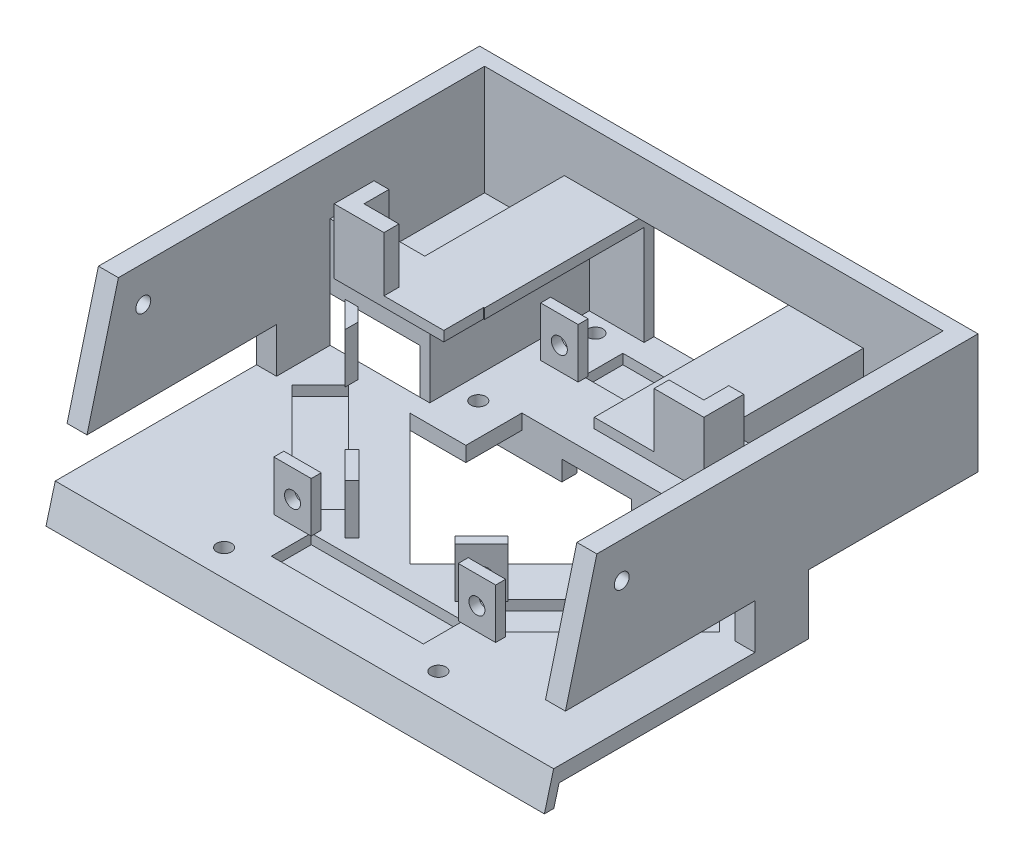
SolidWorks part; units mm, degrees
ref_plane "Plano frontal" through (0, 0, 0) normal (0, 0, 1) x (1, 0, 0)
ref_plane "Plano superior" through (0, 0, 0) normal (0, 1, 0) x (1, 0, 0)
ref_plane "Plano direito" through (0, 0, 0) normal (1, 0, 0) x (0, 0, -1)
sketch "Esboço1" plane through (0, 0, 0) normal (1, 0, 0) x (0, 0, -1)
  line L0 (0, 0) -> (52.75, 0)
  line L1 (0, 0) -> (17.0884, 63.7748)
  line L2 (52.75, 0) -> (52.75, 3)
  line L3 (52.75, 3) -> (3.9097, 3)
  line L4 (17.0884, 63.7748) -> (19.9862, 62.9984)
  line L5 (19.9862, 62.9984) -> (3.9097, 3)
  dimension "D1" = 75
  dimension "D2" = 52.75
  dimension "D3" = 3
  dimension "D4" = 3
extrude "Ressalto-extrusão1" add sketch "Esboço1" along normal blind 100
sketch "Esboço3" plane through (0, 3, 0) normal (0, 1, 0) x (1, 0, 0)
  line L0 (100, 52.75) -> (0, 52.75) construction
  line L1 (22, 52.75) -> (78, 52.75)
  line L2 (22, 52.75) -> (22, 86.75)
  line L3 (22, 86.75) -> (78, 86.75)
  line L4 (78, 52.75) -> (78, 86.75)
  dimension "D1" = 56
  dimension "D2" = 34
  dimension "D3" = 22
extrude "Ressalto-extrusão2" add sketch "Esboço3" against normal blind 3
sketch "Esboço5" plane through (100, 0, 0) normal (1, 0, 0) x (0, 0, -1)
  line L1 (0, 0) -> (52.75, 0) construction
  line L3 (3.9097, 3) -> (1.6041, 3)
  line L4 (1.6041, 3) -> (0.8002, 0)
  line L5 (0.8002, 0) -> (0, 0)
  line L6 (0, 0) -> (17.0884, 63.7748)
  line L7 (17.0884, 63.7748) -> (19.9862, 62.9984)
  line L8 (19.9862, 62.9984) -> (3.9097, 3)
extrude "Corte-extrusão1" cut sketch "Esboço5" against normal blind 100
sketch "Esboço6" plane through (100, 0, 0) normal (1, 0, 0) x (0, 0, -1)
  line L0 (1.649, -3.9196) -> (-0.25, -3.9196)
  line L1 (-0.25, -3.9196) -> (0.8002, 0)
  line L2 (0.8002, 0) -> (2.7002, 0)
  line L3 (0.8002, 0) -> (52.75, 0) construction
  line L4 (2.7002, 0) -> (1.649, -3.9196)
  dimension "D1" = 1.9
extrude "Ressalto-extrusão4" add sketch "Esboço6" against normal blind 100
sketch "Esboço13" plane through (0, 3, 0) normal (0, 1, 0) x (1, 0, 0)
  line L0 (35, 37.75) -> (50, 22.75)
  line L1 (35, 60.2384) -> (65, 60.2384)
  line L2 (35, 60.2384) -> (35, 48.9942)
  line L4 (65, 60.2384) -> (65, 48.9942)
  line L5 (65, 37.75) -> (50, 22.75)
  line L6 (35, 37.75) -> (23.7558, 48.9942)
  line L7 (23.7558, 48.9942) -> (35, 48.9942)
  line L8 (65, 37.75) -> (76.2442, 48.9942)
  line L9 (76.2442, 48.9942) -> (65, 48.9942)
extrude "Corte-extrusão3" cut sketch "Esboço13" against normal through all
sketch "Esboço14" plane through (78, 0, 0) normal (1, 0, 0) x (0, 0, -1)
  line L0 (52.75, 0) -> (86.75, 0) construction
  line L1 (60.2384, -4.9963) -> (63.2384, -4.9963)
  line L2 (60.2384, -4.9963) -> (60.2384, 0)
  line L3 (60.2384, 0) -> (63.2384, 0)
  line L5 (63.2384, 0) -> (65.5807, 0)
  line L6 (79.2384, -4.9963) -> (76.2384, -4.9963)
  line L7 (79.2384, -4.9963) -> (79.2384, 0.0037)
  line L8 (79.2384, 0.0037) -> (76.2384, 0.0037)
  line L10 (76.2384, 0.0037) -> (73.8962, 0)
  arc A1 (76.2384, -4.9963) -> (73.8962, 0) centre (69.7384, -4.9963) ccw
  arc A2 (65.5807, 0) -> (63.2384, -4.9963) centre (69.7384, -4.9963) ccw
  dimension "D1" = 3
  dimension "D2" = 5
extrude "Ressalto-extrusão7" add sketch "Esboço14" against normal blind 56
sketch "Esboço15" plane through (0, 3, 0) normal (0, 1, 0) x (1, 0, 0)
  line L0 (22, 60.2384) -> (28.5, 60.2384) construction
  line L1 (22, 60.2384) -> (35, 60.2384) construction
  line L2 (22, 79.2384) -> (28.5, 79.2384) construction
  line L4 (78, 79.2384) -> (22, 79.2384) construction
  line L6 (28.5, 79.2384) -> (28.5, 81.4934) construction
  line L7 (28.5, 60.2384) -> (28.5, 57.9834) construction
  line L8 (78, 79.2384) -> (71.5, 79.2384) construction
  line L9 (28.5, 81.4934) -> (71.5, 81.4934) construction
  line L10 (71.5, 81.4934) -> (71.5, 57.9834) construction
  circle A0 centre (28.5, 81.4934) radius 1.5
  circle A1 centre (28.5, 57.9834) radius 1.5
  circle A2 centre (71.5, 81.4934) radius 1.5
  circle A3 centre (71.5, 57.9834) radius 1.5
  dimension "D2" = 3
  dimension "D4" = 3
  dimension "D6" = 3
  dimension "D7" = 3
  dimension "D1" = 2.255
  dimension "D3" = 2.255
  dimension "D5" = 6.5
extrude "Corte-extrusão4" cut sketch "Esboço15" against normal through all
sketch "Esboço16" plane through (0, 3, 0) normal (0, 1, 0) x (1, 0, 0)
  line L0 (28.5, 57.9834) -> (28.5, 6.9834) construction
  line L1 (71.5, 57.9834) -> (71.5, 6.9834) construction
  circle A0 centre (28.5, 6.9834) radius 1.5
  circle A2 centre (71.5, 6.9834) radius 1.5
  dimension "D3" = 3
  dimension "D4" = 3
  dimension "D1" = 51
  dimension "D2" = 51
extrude "Corte-extrusão5" cut sketch "Esboço16" against normal through all
sketch "Esboço17" plane through (0, 3, 0) normal (0, 1, 0) x (1, 0, 0)
  line L3 (34.75, 10.2166) -> (65.25, 10.2166)
  line L4 (34.75, 10.2166) -> (34.75, 18.2166)
  line L5 (34.75, 18.2166) -> (65.25, 18.2166)
  line L6 (65.25, 10.2166) -> (65.25, 18.2166)
  dimension "D3" = 30.5
  dimension "D4" = 8
extrude "Corte-extrusão6" cut sketch "Esboço17" against normal blind 2
sketch "Esboço18" plane through (0, 3, 0) normal (0, 1, 0) x (1, 0, 0)
  line L0 (7.105, 41.9998) -> (7.4586, 42.3533)
  line L2 (7.105, 41.9998) -> (28.6718, 20.433)
  line L3 (28.6718, 20.433) -> (34.3286, 26.0899)
  line L8 (7.4586, 42.3533) -> (12.7619, 47.6566)
  line L10 (12.8706, 47.5479) -> (34.3286, 26.0899)
  line L11 (12.7619, 47.6566) -> (12.8706, 47.5479)
  line L13 (0, 41.9998) -> (18.4187, 41.9998) construction
  line L16 (0, 52.75) -> (0, 1.6041) construction
  line L17 (92.89, 41.9998) -> (87.2331, 47.6566)
  line L19 (87.2331, 47.6566) -> (65.6664, 26.0899)
  line L21 (65.6664, 26.0899) -> (71.3232, 20.433)
  line L22 (71.3232, 20.433) -> (92.89, 41.9998)
  dimension "D1" = 8
  dimension "D2" = 0.5
  dimension "D4" = 30.5
extrude "Corte-extrusão7" cut sketch "Esboço18" against normal blind 2
sketch "Esboço19" plane through (0, 3, 0) normal (0, 1, 0) x (1, 0, 0)
  line L6 (65.25, 72.75) -> (34.75, 72.75)
  line L7 (65.25, 72.75) -> (65.25, 80.75)
  line L8 (65.25, 80.75) -> (34.75, 80.75)
  line L9 (34.75, 72.75) -> (34.75, 80.75)
  dimension "D3" = 8
  dimension "D4" = 30.5
extrude "Corte-extrusão8" cut sketch "Esboço19" against normal blind 2
sketch "Esboço20" plane through (0, 0, -60.2384) normal (0, 0, 1) x (1, 0, 0)
  line L0 (22, -4.9963) -> (50, -4.9963) construction
  line L10 (50, -4.9963) -> (43, -4.9963)
  line L11 (43, -4.9963) -> (43, -0.9963)
  line L12 (43, -0.9963) -> (57, -0.9963)
  line L13 (57, -0.9963) -> (57, -4.9963)
  line L14 (22, -4.9963) -> (78, -4.9963) construction
  line L15 (57, -4.9963) -> (50, -4.9963)
  dimension "D1" = 28
  dimension "D2" = 7
  dimension "D3" = 4
  dimension "D4" = 14
extrude "Corte-extrusão10" cut sketch "Esboço20" against normal blind 6
sketch "Esboço25" plane through (0, 3, 0) normal (0, 1, 0) x (1, 0, 0)
  line L0 (35.27, 67.25) -> (35.27, 72.25) construction
  line L1 (27.75, 73.25) -> (35.27, 73.25)
  line L2 (27.75, 73.25) -> (27.75, 71.25)
  line L3 (27.75, 71.25) -> (35.27, 71.25)
  line L4 (35.27, 73.25) -> (35.27, 71.25)
  line L5 (92.5364, 52.2528) -> (89.8848, 49.6012) construction
  line L6 (64.75, 73.25) -> (72.25, 73.25)
  line L7 (64.75, 73.25) -> (64.75, 71.25)
  line L8 (64.75, 71.25) -> (72.25, 71.25)
  line L9 (72.25, 73.25) -> (72.25, 71.25)
  line L11 (87.2331, 46.9495) -> (87.2331, 49.6012)
  line L12 (89.8848, 52.2528) -> (92.5364, 52.2528)
  line L14 (93.5971, 51.1921) -> (92.5364, 52.2528) construction
  line L15 (87.2331, 46.9495) -> (92.5364, 52.2528)
  line L16 (61.0702, 20.7866) -> (66.3735, 26.0899)
  line L17 (66.3735, 26.0899) -> (64.9593, 27.5041)
  line L18 (64.9593, 27.5041) -> (59.656, 22.2008)
  line L19 (59.656, 22.2008) -> (61.0702, 20.7866)
  line L20 (33.6215, 26.0899) -> (38.9248, 20.7866)
  line L21 (38.9248, 20.7866) -> (40.339, 22.2008)
  line L22 (40.339, 22.2008) -> (35.0357, 27.5041)
  line L23 (35.0357, 27.5041) -> (33.6215, 26.0899)
  line L24 (7.4586, 52.2528) -> (12.7619, 46.9495)
  line L26 (12.7619, 46.9495) -> (12.7619, 49.6012)
  line L27 (10.1102, 52.2528) -> (7.4586, 52.2528)
  line L29 (10.1102, 52.2528) -> (12.7619, 49.6012)
  line L30 (64.75, 17.7166) -> (72.25, 17.7166)
  line L31 (64.75, 17.7166) -> (64.75, 19.7166)
  line L32 (64.75, 19.7166) -> (72.25, 19.7166)
  line L33 (72.25, 17.7166) -> (72.25, 19.7166)
  line L34 (27.75, 17.7166) -> (35.25, 17.7166)
  line L35 (27.75, 17.7166) -> (27.75, 19.7166)
  line L36 (27.75, 19.7166) -> (35.25, 19.7166)
  line L37 (35.25, 17.7166) -> (35.25, 19.7166)
  line L38 (87.2331, 49.6012) -> (89.8848, 52.2528)
  dimension "D1" = 2
  dimension "D2" = 2
  dimension "D3" = 2
  dimension "D4" = 2
  dimension "D5" = 2
  dimension "D6" = 2
sketch "Esboço38" plane through (0, 3, 0) normal (0, 1, 0) x (1, 0, 0)
  line L0 (78, 86.75) -> (22, 86.75) construction
  line L1 (22, 86.75) -> (35, 86.75)
  line L2 (22, 86.75) -> (22, 84.75)
  line L3 (22, 84.75) -> (35, 84.75)
  line L4 (35, 86.75) -> (35, 84.75)
  line L5 (22, 86.75) -> (22, 52.75) construction
  line L6 (78, 52.75) -> (78, 86.75) construction
  line L11 (78, 86.75) -> (65, 86.75)
  line L12 (78, 86.75) -> (78, 84.75)
  line L13 (78, 84.75) -> (65, 84.75)
  line L14 (65, 86.75) -> (65, 84.75)
  dimension "D1" = 13
  dimension "D2" = 13
extrude "Ressalto-extrusão15" add sketch "Esboço38" along normal blind 20
sketch "Esboço40" plane through (100, 0, 0) normal (1, 0, 0) x (0, 0, -1)
  line L0 (52.75, 3) -> (52.75, 25)
  line L5 (5.9487, 19.4211) -> (7.4028, 25)
  line L6 (52.75, 0) -> (52.75, 3) construction
  line L7 (52.75, 3) -> (1.6041, 3) construction
  line L9 (52.75, 3) -> (41.9998, 3)
  line L10 (41.9998, 3) -> (41.9998, 12)
  line L11 (41.9998, 12) -> (3.969, 11.8258)
  line L12 (3.969, 11.8258) -> (5.9487, 19.4211)
  line L13 (52.75, 25) -> (52.75, 36)
  line L14 (7.4028, 25) -> (10.2699, 36)
  line L16 (10.2699, 36) -> (52.75, 36)
  dimension "D1" = 9
  dimension "D2" = 11
extrude "Ressalto-extrusão16" add sketch "Esboço40" against normal blind 4
sketch "Esboço41" plane through (0, 0, 0) normal (-1, 0, 0) x (0, 0, 1)
  line L0 (-52.75, 3) -> (-52.75, 25)
  line L1 (-52.75, 0) -> (-52.75, 3) construction
  line L2 (-52.75, 3) -> (-52.75, 36) construction
  line L6 (-3.969, 11.8258) -> (-41.9998, 12) construction
  line L7 (-3.969, 11.8258) -> (-41.9998, 12)
  line L8 (-41.9998, 12) -> (-41.9998, 3) construction
  line L9 (-41.9998, 12) -> (-41.9998, 3)
  line L10 (-52.75, 3) -> (-1.6041, 3) construction
  line L11 (-41.9998, 3) -> (-52.75, 3)
  line L12 (-52.75, 25) -> (-52.75, 36)
  line L13 (-52.75, 36) -> (-10.2699, 36)
  line L14 (-7.4028, 25) -> (-3.969, 11.8258)
  line L15 (-7.4028, 25) -> (-10.2699, 36)
  dimension "D1" = 11
extrude "Ressalto-extrusão17" add sketch "Esboço41" against normal blind 4
sketch "Esboço43" plane through (78, 0, 0) normal (1, 0, 0) x (0, 0, -1)
  line L0 (86.75, 0) -> (86.75, 23) construction
  line L1 (86.75, 23) -> (52.75, 23)
  line L2 (86.75, 23) -> (86.75, 25)
  line L3 (86.75, 25) -> (52.75, 25)
  line L4 (52.75, 23) -> (52.75, 25)
  line L5 (84.75, 23) -> (86.75, 23) construction
  line L6 (52.75, 0) -> (52.75, 36) construction
  dimension "D1" = 2
extrude "Ressalto-extrusão18" add sketch "Esboço43" against normal blind 13
sketch "Esboço45" plane through (22, 0, 0) normal (-1, 0, 0) x (0, 0, 1)
  line L0 (-86.75, 23) -> (-84.75, 23) construction
  line L1 (-86.75, 23) -> (-52.75, 23)
  line L2 (-86.75, 23) -> (-86.75, 25)
  line L3 (-86.75, 25) -> (-52.75, 25)
  line L4 (-52.75, 23) -> (-52.75, 25)
  line L5 (-86.75, 0) -> (-86.75, 23) construction
  line L6 (-52.75, 0) -> (-52.75, 36) construction
  line L7 (-86.75, 25) -> (-52.75, 25) construction
extrude "Ressalto-extrusão19" add sketch "Esboço45" against normal blind 13
sketch "Esboço46" plane through (78, 0, 0) normal (1, 0, 0) x (0, 0, -1)
  line L0 (52.75, 0) -> (52.75, 36) construction
  line L1 (84.75, 3) -> (52.75, 3)
  line L2 (84.75, 3) -> (84.75, 14)
  line L3 (84.75, 14) -> (52.75, 14)
  line L4 (52.75, 3) -> (52.75, 14)
  dimension "D1" = 11
extrude "Ressalto-extrusão20" add sketch "Esboço46" against normal blind 2
sketch "Esboço47" plane through (0, 0, -52.75) normal (0, 0, -1) x (-1, 0, 0)
  line L0 (-100, 0) -> (-100, 36) construction
  line L1 (-78, 14) -> (-100, 14)
  line L2 (-78, 14) -> (-78, 12)
  line L3 (-78, 12) -> (-100, 12)
  line L4 (-100, 14) -> (-100, 12)
  dimension "D1" = 2
extrude "Ressalto-extrusão21" add sketch "Esboço47" along normal blind 34
sketch "Esboço48" plane through (22, 0, 0) normal (-1, 0, 0) x (0, 0, 1)
  line L5 (-84.75, 3) -> (-52.75, 3)
  line L6 (-84.75, 3) -> (-84.75, 14)
  line L7 (-84.75, 14) -> (-52.75, 14)
  line L8 (-52.75, 3) -> (-52.75, 14)
extrude "Ressalto-extrusão22" add sketch "Esboço48" against normal blind 2
sketch "Esboço49" plane through (22, 0, 0) normal (-1, 0, 0) x (0, 0, 1)
  line L1 (-52.75, 14) -> (-84.75, 14)
  line L2 (-52.75, 14) -> (-52.75, 12)
  line L3 (-52.75, 12) -> (-84.75, 12)
  line L4 (-84.75, 14) -> (-84.75, 12)
  dimension "D1" = 2
extrude "Ressalto-extrusão23" add sketch "Esboço49" along normal blind 22
sketch "Esboço51" plane through (0, 0, -86.75) normal (0, 0, -1) x (-1, 0, 0)
  line L0 (-76, 14) -> (-96, 14) construction
  line L1 (-76, 14) -> (-78, 14)
  line L2 (-76, 14) -> (-76, 23)
  line L3 (-76, 23) -> (-78, 23)
  line L5 (-78, 25) -> (-80, 25)
  line L6 (-78, 25) -> (-78, 14)
  line L7 (-78, 14) -> (-80, 14)
  line L8 (-80, 25) -> (-80, 14)
  line L9 (-24, 14) -> (-4, 14) construction
  line L10 (-24, 14) -> (-22, 14)
  line L11 (-24, 14) -> (-24, 23)
  line L12 (-24, 23) -> (-22, 23)
  line L14 (-22, 25) -> (-20, 25)
  line L15 (-22, 25) -> (-22, 14)
  line L16 (-22, 14) -> (-20, 14)
  line L17 (-20, 25) -> (-20, 14)
  dimension "D1" = 2
  dimension "D2" = 2
extrude "Ressalto-extrusão32" add sketch "Esboço51" against normal blind 34 contours L17 L14 L8 L16 | L12 L11 L10 L8 | L2 L3 L12 L1 | L5 L8 L2 L12 region at (77, 18.5, -86.75) region at (79, 19.5, -86.75) region at (23, 18.5, -86.75) region at (21, 19.5, -86.75)
sketch "Esboço53" plane through (0, 14, 0) normal (0, 1, 0) x (1, 0, 0)
  line L0 (20, 52.75) -> (20, 84.75) construction
  line L1 (0, 52.75) -> (20, 52.75)
  line L2 (0, 52.75) -> (0, 55.75)
  line L3 (0, 55.75) -> (20, 55.75)
  line L4 (20, 52.75) -> (20, 55.75)
  line L5 (80, 52.75) -> (80, 86.75) construction
  line L6 (100, 52.75) -> (80, 52.75)
  line L7 (100, 52.75) -> (100, 55.75)
  line L8 (100, 55.75) -> (80, 55.75)
  line L9 (80, 52.75) -> (80, 55.75)
  dimension "D1" = 3
  dimension "D2" = 3
extrude "Ressalto-extrusão33" add sketch "Esboço53" along normal blind 11
sketch "Esboço55" plane through (0, 0, -86.75) normal (0, 0, -1) x (-1, 0, 0)
  line L1 (-80, 25) -> (-100, 25)
  line L2 (-80, 25) -> (-80, 14)
  line L3 (-80, 14) -> (-100, 14)
  line L4 (-100, 25) -> (-100, 14)
  line L5 (-20, 25) -> (0, 25)
  line L6 (-20, 25) -> (-20, 14)
  line L7 (-20, 14) -> (0, 14)
  line L8 (0, 25) -> (0, 14)
extrude "Ressalto-extrusão34" add sketch "Esboço55" against normal blind 3
sketch "Esboço56" plane through (0, 14, 0) normal (0, 1, 0) x (1, 0, 0)
  line L0 (20, 55.75) -> (0, 55.75) construction
  line L1 (0, 83.75) -> (4, 83.75)
  line L2 (0, 83.75) -> (0, 55.75)
  line L3 (0, 55.75) -> (4, 55.75)
  line L4 (4, 83.75) -> (4, 55.75)
  line L5 (100, 55.75) -> (80, 55.75) construction
  line L6 (100, 83.75) -> (96, 83.75)
  line L7 (100, 83.75) -> (100, 55.75)
  line L8 (100, 55.75) -> (96, 55.75)
  line L9 (96, 83.75) -> (96, 55.75)
extrude "Ressalto-extrusão35" add sketch "Esboço56" along normal blind 22
sketch "Esboço57" plane through (0, 25, 0) normal (0, 1, 0) x (1, 0, 0)
  line L1 (0, 86.75) -> (100, 86.75)
  line L2 (0, 86.75) -> (0, 83.75)
  line L3 (0, 83.75) -> (100, 83.75)
  line L4 (100, 86.75) -> (100, 83.75)
extrude "Ressalto-extrusão36" add sketch "Esboço57" along normal blind 11
sketch "Esboço59" plane through (0, 25, 0) normal (0, 1, 0) x (1, 0, 0)
  line L1 (0, 55.75) -> (4, 55.75)
  line L2 (0, 55.75) -> (0, 52.75)
  line L3 (0, 52.75) -> (4, 52.75)
  line L4 (4, 55.75) -> (4, 52.75)
  line L5 (100, 52.75) -> (96, 52.75)
  line L6 (100, 52.75) -> (100, 55.75)
  line L7 (100, 55.75) -> (96, 55.75)
  line L8 (96, 52.75) -> (96, 55.75)
extrude "Ressalto-extrusão38" add sketch "Esboço59" along normal blind 11
sketch "Esboço60" plane through (0, 0, 0) normal (-1, 0, 0) x (0, 0, 1)
  line L1 (-84.75, 14) -> (-86.75, 14)
  line L2 (-84.75, 14) -> (-84.75, 12)
  line L3 (-84.75, 12) -> (-86.75, 12)
  line L4 (-86.75, 14) -> (-86.75, 12)
extrude "Ressalto-extrusão39" add sketch "Esboço60" against normal blind 22
extrude "Ressalto-extrusão11" add sketch "Esboço25" along normal blind 10
sketch "Esboço26" plane through (0, 0, -17.7166) normal (0, 0, 1) x (1, 0, 0)
  line L0 (68.4948, 2) -> (68.4948, 13) construction
  line L1 (31.5002, 13) -> (31.5002, 2) construction
  circle A0 centre (68.4948, 7.5) radius 1.6
  circle A1 centre (31.5002, 7.5) radius 1.5998
  dimension "D1" = 3.2
extrude "Corte-extrusão11" cut sketch "Esboço26" against normal blind 58
sketch "Esboço27" plane through (29.8557, 0, -29.8557) normal (-0.7071, 0, 0.7071) x (0.7071, 0, 0.7071)
  circle A0 centre (-27.9243, 7.5) radius 1.6
  circle A1 centre (9.0757, 7.5) radius 1.6
extrude "Corte-extrusão12" cut sketch "Esboço27" against normal blind 10
sketch "Esboço28" plane through (20.1418, 0, 20.1418) normal (0.7071, 0, 0.7071) x (0.7071, 0, -0.7071)
  circle A0 centre (98.6315, 7.5) radius 1.6
  circle A1 centre (61.6315, 7.5) radius 1.6
extrude "Corte-extrusão13" cut sketch "Esboço28" against normal blind 10
sketch "Esboço62" plane through (0, 0, -52.75) normal (0, 0, 1) x (1, 0, 0)
  line L0 (35, 23) -> (24, 23) construction
  line L1 (34.8133, 23) -> (12.8133, 23)
  line L2 (34.8133, 23) -> (34.8133, 25)
  line L3 (34.8133, 25) -> (12.8133, 25)
  line L4 (12.8133, 23) -> (12.8133, 25)
  line L5 (35, 25) -> (4, 25) construction
  line L6 (65, 23) -> (76, 23) construction
  line L7 (65, 23) -> (87, 23)
  line L8 (65, 23) -> (65, 25)
  line L9 (65, 25) -> (87, 25)
  line L10 (87, 23) -> (87, 25)
  line L11 (65, 25) -> (96, 25) construction
  dimension "D1" = 22
  dimension "D2" = 22
extrude "Ressalto-extrusão40" add sketch "Esboço62" along normal blind 8
sketch "Esboço63" plane through (0, 25, 0) normal (0, 1, 0) x (1, 0, 0)
  line L0 (12.8133, 52.75) -> (4, 52.75) construction
  line L1 (12.8133, 52.75) -> (15.8133, 52.75)
  line L2 (12.8133, 52.75) -> (12.8133, 44.75)
  line L3 (12.8133, 44.75) -> (22.8133, 44.75)
  line L4 (22.8133, 47.75) -> (22.8133, 44.75)
  line L5 (12.8133, 44.75) -> (12.8133, 52.75) construction
  line L6 (34.8133, 44.75) -> (12.8133, 44.75) construction
  line L7 (87, 44.75) -> (87, 52.75) construction
  line L8 (87, 44.75) -> (77, 44.75)
  line L9 (87, 44.75) -> (87, 52.75)
  line L10 (87, 52.75) -> (84, 52.75)
  line L11 (77, 44.75) -> (77, 47.75)
  line L12 (22.8133, 44.75) -> (22.8133, 47.75)
  line L13 (15.8133, 52.75) -> (15.8133, 47.75)
  line L14 (22.8133, 47.75) -> (15.8133, 47.75)
  line L18 (77, 44.75) -> (77, 47.75)
  line L20 (77, 47.75) -> (84, 47.75)
  line L23 (84, 47.75) -> (84, 52.75)
  line M17 (12.8133, 52.75) -> (12.8133, 44.75)
  line M18 (12.8133, 44.75) -> (34.8133, 44.75)
  dimension "D1" = 10
  dimension "D2" = 10
  dimension "D3" = 3
extrude "Ressalto-extrusão41" add sketch "Esboço63" along normal blind 11 contours L23 L20 L11 L8 L9 L10 | L4 L14 L13 L1 M17 M18 region at (16.6466, 25, -47.5833) region at (83.1667, 25, -47.5833)
sketch "Esboço64" plane through (100, 0, 0) normal (1, 0, 0) x (0, 0, -1)
  circle A0 centre (15.2699, 28.8258) radius 1.5
  dimension "D1" = 3
  dimension "D2" = 5
  dimension "D3" = 17
extrude "Corte-extrusão14" cut sketch "Esboço64" against normal through all
